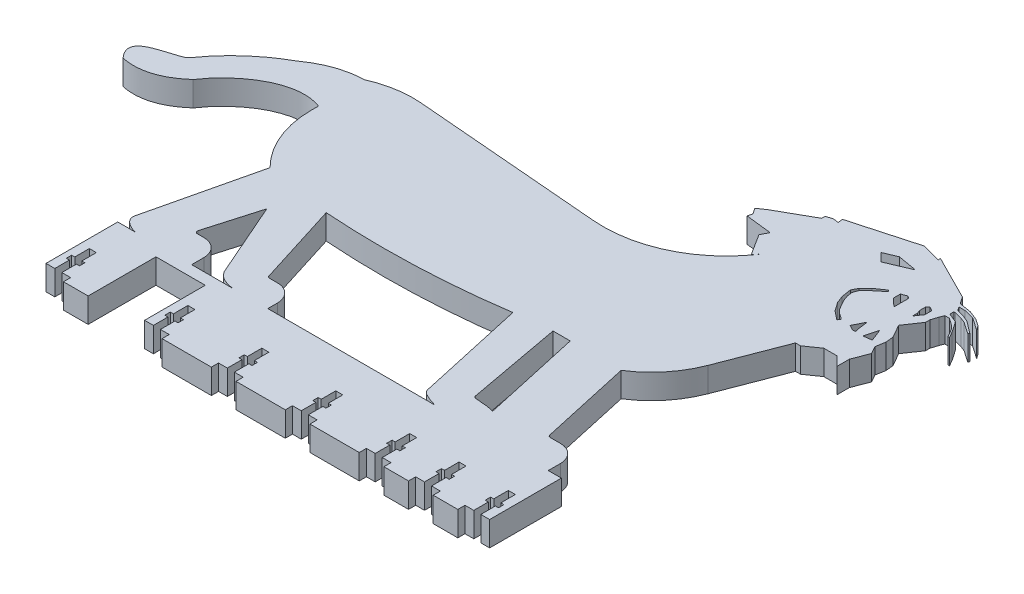
SolidWorks part; units mm, degrees
ref_plane "Front Plane" through (0, 0, 0) normal (0, 0, 1) x (1, 0, 0)
ref_plane "Top Plane" through (0, 0, 0) normal (0, 1, 0) x (1, 0, 0)
ref_plane "Right Plane" through (0, 0, 0) normal (1, 0, 0) x (0, 0, -1)
sketch "Sketch1" plane through (0, 0, 0) normal (0, 1, 0) x (1, 0, 0)
  line L0 (90, -48.4544) -> (80, -48.4544)
  line L1 (90, -48.4544) -> (-90, -48.4544)
  line L2 (90, -48.4544) -> (90, 48.4544)
  line L3 (90, 48.4544) -> (-90, 48.4544)
  line L4 (-90, -48.4544) -> (-90, 48.4544)
  line L5 (90, -48.4544) -> (-90, 48.4544) construction
  line L6 (90, 48.4544) -> (-90, -48.4544) construction
  line L7 (80, -48.4544) -> (80, -51.3617)
  line L8 (80, -51.3617) -> (70, -51.3617)
  line L9 (70, -51.3617) -> (70, -48.4544)
  line L10 (70, -48.4544) -> (60, -48.4544)
  line L11 (60, -48.4544) -> (60, -51.3617)
  line L12 (60, -51.3617) -> (50, -51.3617)
  line L13 (50, -51.3617) -> (50, -48.4544)
  line L14 (50, -48.4544) -> (40, -48.4544)
  line L15 (40, -48.4544) -> (40, -51.3617)
  line L16 (40, -51.3617) -> (20, -51.3617)
  line L17 (20, -51.3617) -> (20, -48.4544)
  line L18 (20, -48.4544) -> (10, -48.4544)
  line L19 (10, -48.4544) -> (10, -51.3617)
  line L20 (10, -51.3617) -> (-10, -51.3617)
  line L21 (-10, -51.3617) -> (-10, -48.4544)
  line L22 (-10, -48.4544) -> (-20, -48.4544)
  line L23 (-20, -48.4544) -> (-20, -51.3617)
  line L24 (-20, -51.3617) -> (-40, -51.3617)
  line L25 (-40, -51.3617) -> (-40, -48.4544)
  line L26 (-40, -48.4544) -> (-50, -48.4544)
  line L27 (-50, -48.4544) -> (-50, -23.8396)
  line L28 (-50, -23.8396) -> (-70, -23.8396)
  line L29 (-70, -23.8396) -> (-70, -48.4544)
  line L30 (-70, -48.4544) -> (-70, -51.3617)
  line L31 (-70, -51.3617) -> (-80, -51.3617)
  line L32 (-80, -51.3617) -> (-80, -48.4544)
  line L33 (-80, -48.4544) -> (-90, -48.4544)
  point P0 (0, 0)
  dimension "D1" = 10
  dimension "D2" = 10
  dimension "D3" = 10
  dimension "D4" = 10
  dimension "D5" = 10
  dimension "D6" = 20
  dimension "D7" = 10
  dimension "D8" = 20
  dimension "D9" = 10
  dimension "D10" = 20
  dimension "D11" = 10
  dimension "D12" = 20
  dimension "D13" = 10
  dimension "D14" = 10
extrude "Boss-Extrude1" add sketch "Sketch1" along normal blind 10 contours L29 L28 L27 L1 L0 L2 L3 L4 | L32 L31 L30 L1 | L25 L24 L23 L1 | L21 L20 L19 L1 | L17 L16 L15 L1 | L13 L12 L11 L1 | L9 L8 L7 L1 region at (1.7425, 0, -1.0498) region at (75, 0, 49.908) region at (55, 0, 49.908) region at (-75, 0, 49.908) region at (30, 0, 49.908) region at (0, 0, 49.908) region at (-30, 0, 49.908)
sketch "Sketch3" plane through (0, 10, 0) normal (0, 1, 0) x (1, 0, 0)
  line L0 (-80, -48.4544) -> (-90, -48.4544) construction
  line L1 (-86.425, -48.4544) -> (-83.575, -48.4544)
  line L2 (-86.425, -48.4544) -> (-86.425, -34.4544)
  line L3 (-86.425, -34.4544) -> (-83.575, -34.4544)
  line L4 (-83.575, -48.4544) -> (-83.575, -34.4544)
  line L5 (-90, -48.4544) -> (-90, 48.4544) construction
  line L6 (-87.675, -40.3544) -> (-82.325, -40.3544)
  line L7 (-87.675, -40.3544) -> (-87.675, -42.5544)
  line L8 (-87.675, -42.5544) -> (-82.325, -42.5544)
  line L9 (-82.325, -40.3544) -> (-82.325, -42.5544)
  line L10 (-46.425, -48.4544) -> (-43.575, -48.4544)
  line L11 (-46.425, -48.4544) -> (-46.425, -34.4544)
  line L12 (-46.425, -34.4544) -> (-43.575, -34.4544)
  line L13 (-43.575, -48.4544) -> (-43.575, -34.4544)
  line L14 (-47.675, -40.3544) -> (-42.325, -40.3544)
  line L15 (-47.675, -40.3544) -> (-47.675, -42.5544)
  line L16 (-47.675, -42.5544) -> (-42.325, -42.5544)
  line L17 (-42.325, -40.3544) -> (-42.325, -42.5544)
  line L18 (-40, -48.4544) -> (-50, -48.4544) construction
  line L19 (-50, -48.4544) -> (-50, -23.8396) construction
  line L20 (-16.425, -48.4544) -> (-13.575, -48.4544)
  line L21 (-16.425, -48.4544) -> (-16.425, -34.4544)
  line L22 (-16.425, -34.4544) -> (-13.575, -34.4544)
  line L23 (-13.575, -48.4544) -> (-13.575, -34.4544)
  line L24 (-17.675, -40.3544) -> (-12.325, -40.3544)
  line L25 (-17.675, -40.3544) -> (-17.675, -42.5544)
  line L26 (-17.675, -42.5544) -> (-12.325, -42.5544)
  line L27 (-12.325, -40.3544) -> (-12.325, -42.5544)
  line L28 (13.575, -48.4544) -> (16.425, -48.4544)
  line L29 (13.575, -48.4544) -> (13.575, -34.4544)
  line L30 (13.575, -34.4544) -> (16.425, -34.4544)
  line L31 (16.425, -48.4544) -> (16.425, -34.4544)
  line L32 (12.325, -40.3544) -> (17.675, -40.3544)
  line L33 (12.325, -40.3544) -> (12.325, -42.5544)
  line L34 (12.325, -42.5544) -> (17.675, -42.5544)
  line L35 (17.675, -40.3544) -> (17.675, -42.5544)
  line L36 (43.575, -48.4544) -> (46.425, -48.4544)
  line L37 (43.575, -48.4544) -> (43.575, -34.4544)
  line L38 (43.575, -34.4544) -> (46.425, -34.4544)
  line L39 (46.425, -48.4544) -> (46.425, -34.4544)
  line L40 (42.325, -40.3544) -> (47.675, -40.3544)
  line L41 (42.325, -40.3544) -> (42.325, -42.5544)
  line L42 (42.325, -42.5544) -> (47.675, -42.5544)
  line L43 (47.675, -40.3544) -> (47.675, -42.5544)
  line L44 (63.575, -48.4544) -> (66.425, -48.4544)
  line L45 (63.575, -48.4544) -> (63.575, -34.4544)
  line L46 (63.575, -34.4544) -> (66.425, -34.4544)
  line L47 (66.425, -48.4544) -> (66.425, -34.4544)
  line L48 (62.325, -40.3544) -> (67.675, -40.3544)
  line L49 (62.325, -40.3544) -> (62.325, -42.5544)
  line L50 (62.325, -42.5544) -> (67.675, -42.5544)
  line L51 (67.675, -40.3544) -> (67.675, -42.5544)
  line L52 (83.575, -48.4544) -> (86.425, -48.4544)
  line L53 (83.575, -48.4544) -> (83.575, -34.4544)
  line L54 (83.575, -34.4544) -> (86.425, -34.4544)
  line L55 (86.425, -48.4544) -> (86.425, -34.4544)
  line L56 (82.325, -40.3544) -> (87.675, -40.3544)
  line L57 (82.325, -40.3544) -> (82.325, -42.5544)
  line L58 (82.325, -42.5544) -> (87.675, -42.5544)
  line L59 (87.675, -40.3544) -> (87.675, -42.5544)
  line L60 (90, -48.4544) -> (80, -48.4544) construction
  line L61 (90, -48.4544) -> (90, 48.4544) construction
  line L62 (70, -48.4544) -> (60, -48.4544) construction
  line L63 (70, -51.3617) -> (70, -48.4544) construction
  line L64 (50, -48.4544) -> (40, -48.4544) construction
  line L65 (50, -51.3617) -> (50, -48.4544) construction
  line L66 (20, -48.4544) -> (10, -48.4544) construction
  line L67 (20, -51.3617) -> (20, -48.4544) construction
  line L68 (-10, -48.4544) -> (-20, -48.4544) construction
  line L69 (-10, -51.3617) -> (-10, -48.4544) construction
  point P20 (-47.675, -41.4544)
  point P33 (-17.675, -41.4544)
  point P42 (12.325, -41.4544)
  point P51 (42.325, -41.4544)
  point P60 (62.325, -41.4544)
  point P69 (82.325, -41.4544)
  dimension "D1" = 2.85
  dimension "D2" = 5.35
  dimension "D3" = 2.2
  dimension "D4" = 14
  dimension "D5" = 2.325
  dimension "D6" = 3.575
  dimension "D7" = 2.85
  dimension "D8" = 5.35
  dimension "D9" = 2.2
  dimension "D10" = 14
  dimension "D11" = 1.25
  dimension "D12" = 5.9
  dimension "D13" = 5.9
  dimension "D14" = 0
  dimension "D15" = 3.575
  dimension "D16" = 2.85
  dimension "D17" = 5.35
  dimension "D18" = 2.2
  dimension "D19" = 14
  dimension "D20" = 1.25
  dimension "D21" = 5.9
  dimension "D22" = 2.85
  dimension "D23" = 5.35
  dimension "D24" = 2.2
  dimension "D25" = 14
  dimension "D26" = 1.25
  dimension "D27" = 5.9
  dimension "D28" = 2.85
  dimension "D29" = 5.35
  dimension "D30" = 2.2
  dimension "D31" = 14
  dimension "D32" = 1.25
  dimension "D33" = 5.9
  dimension "D34" = 2.85
  dimension "D35" = 5.35
  dimension "D36" = 2.2
  dimension "D37" = 14
  dimension "D38" = 1.25
  dimension "D39" = 5.9
  dimension "D40" = 2.85
  dimension "D41" = 5.35
  dimension "D42" = 2.2
  dimension "D43" = 14
  dimension "D44" = 1.25
  dimension "D45" = 5.9
  dimension "D46" = 0
  dimension "D47" = 3.575
  dimension "D48" = 0
  dimension "D49" = 3.575
  dimension "D50" = 0
  dimension "D51" = 3.575
  dimension "D52" = 0
  dimension "D53" = 3.575
  dimension "D54" = 0
  dimension "D55" = 3.575
extrude "Cut-Extrude1" cut sketch "Sketch3" against normal blind 10 contours L4 L3 L2 L1 | L9 L8 L7 L6 | L13 L12 L11 L10 | L17 L16 L15 L14 | L23 L22 L21 L20 | L27 L26 L25 L24 | L29 L30 L31 L28 | L33 L34 L35 L32 | L39 L38 L37 L36 | L42 L43 L40 L41 | L50 L51 L48 L49 | L45 L46 L47 L44 | L55 L54 L53 L52 | L58 L59 L56 L57
sketch "Sketch5" plane through (0, 10, 0) normal (0, 1, 0) x (1, 0, 0)
  line L0 (-90, -19.3517) -> (90, -19.3517)
  line L1 (-90, -48.4544) -> (-90, 48.4544) construction
  line L2 (90, -48.4544) -> (90, 48.4544) construction
  line L3 (90, -19.3517) -> (90, 140.6483)
  line L4 (90, 140.6483) -> (-150, 140.6483)
  line L5 (-150, 140.6483) -> (-150, -19.3517)
  line L6 (-150, -19.3517) -> (-90, -19.3517)
  line L7 (90, 140.6483) -> (125, 140.6483)
  line L8 (125, 140.6483) -> (125, 75.6483)
  line L9 (125, 75.6483) -> (90, 75.6483)
extrude "Boss-Extrude2" add sketch "Sketch5" against normal blind 10 contours L9 L8 L7 L3 | L5 L6 L0 L3 L4 region at (-30, 10, -60.6483) region at (107.5, 10, -108.1483)
sketch "Sketch7" plane through (0, 10, 0) normal (0, 1, 0) x (1, 0, 0)
  line L0 (-90, -19.3517) -> (90, -19.3517)
  line L1 (90, -48.4544) -> (90, 75.6483) construction
  line L2 (90, -19.3517) -> (90, 30.6483)
  line L3 (90, 30.6483) -> (-150, 30.6483)
  line L4 (-150, 140.6483) -> (-150, -19.3517) construction
  line L5 (-150, 30.6483) -> (-150, -19.3517)
  line L6 (-150, -19.3517) -> (-90, -19.3517)
  line L7 (90, 75.6483) -> (72.685, 30.6483)
  line L8 (72.685, 30.6483) -> (-90, 30.6483)
  line L9 (-90, 30.6483) -> (-90, 85.6483)
  line L10 (-90, 85.6483) -> (29.9691, 75.6483)
  line L11 (29.9691, 75.6483) -> (90, 75.6483)
  line L12 (-78.1918, 30.6483) -> (-90, -19.3517)
  line L13 (-90, -19.3517) -> (-60, -19.3517)
  line L14 (-60, -19.3517) -> (-60, -7.3517)
  line L15 (-60, -7.3517) -> (-71, -7.3517)
  line L16 (-71, -7.3517) -> (-60, 30.6483)
  line L17 (-71, 30.6483) -> (-49.1251, -19.3517)
  line L18 (-49.1251, -19.3517) -> (-29.1251, -19.3517)
  line L19 (-29.1251, -19.3517) -> (-29.1251, -8.3517)
  line L20 (-29.1251, -8.3517) -> (-40.1251, -8.3517)
  line L21 (-40.1251, -8.3517) -> (-52.3654, 30.6483)
  line L22 (64.2673, 30.6483) -> (72.685, -7.3517)
  line L23 (72.685, -7.3517) -> (84.685, -7.3517)
  line L24 (84.685, -7.3517) -> (84.685, -19.3517)
  line L25 (84.685, -19.3517) -> (54.685, -19.3517)
  line L26 (54.685, -19.3517) -> (43.609, 30.6483)
  line L27 (43.609, 30.6483) -> (36.609, 30.6483)
  line L28 (36.609, 30.6483) -> (43.8555, -8.6898)
  line L29 (43.8555, -8.6898) -> (52.3232, -8.6898)
  line L30 (52.3232, -8.6898) -> (54.685, -19.3517)
  line L31 (54.685, -19.3517) -> (32.685, -19.3517)
  line L32 (32.685, -19.3517) -> (21.609, 30.6483)
  line L33 (36.609, 75.6483) -> (59.9846, 112.9165)
  line L34 (59.9846, 112.9165) -> (43.609, 120.0898)
  line L35 (43.609, 120.0898) -> (43.609, 140.6483)
  line L36 (-150, 140.6483) -> (125, 140.6483) construction
  line L37 (43.609, 140.6483) -> (125, 140.6483)
  line L38 (125, 140.6483) -> (125, 75.6483)
  line L39 (125, 75.6483) -> (90, 75.6483) construction
  line L40 (125, 140.6483) -> (125, 75.6483) construction
  line L41 (125, 75.6483) -> (90, 75.6483)
  line L42 (-150, 140.6483) -> (43.609, 140.6483)
  line L43 (-150, 140.6483) -> (-150, 30.6483)
  line L44 (90, 30.6483) -> (90, 75.6483)
  line L45 (90, 30.6483) -> (90, -19.3517)
  spline S0 degree 2 poles (-124.7773, 45.9651) (-135.0303, 36.8919) (-146.5024, 39.3052) knots 0 0 0 1 1 1
  spline S1 degree 3 poles (-146.5024, 39.3052) (-155.6059, 49.4717) (-135.7004, 49.6402) (-133.0933, 52.9985) knots 0 0 0 0 1 1 1 1
  spline S2 degree 3 poles (-124.7773, 45.9651) (-117.8679, 56.3801) (-103.2493, 67.0532) (-90, 62.1051) knots 0 0 0 0 1 1 1 1
  spline S3 degree 2 poles (-133.0933, 52.9985) (-124.0498, 65.827) (-110.4095, 73.4115) knots 0 0 0 1 1 1
  spline S4 degree 2 poles (-110.4095, 73.4115) (-100.1544, 80.8869) (-88.5721, 80.6483) knots 0 0 0 1 1 1
extrude "Cut-Extrude2" cut sketch "Sketch7" against normal blind 10 contours L9 L10 L11 L33 L34 L35 L42 L43 L3 | L3 L44 L7 | L23 L24 L0 L2 L3 L22 | L28 L29 L26 L3 | L0 L32 L3 L21 L20 L19 | L3 L5 L6 L12 L8 | L17 L16 L15 L14 L0 region at (-116.9598, 10, -6.3949) region at (-60.678, 10, 4.6118) region at (-60.7011, 10, -101.7209) region at (-8.0236, 10, -6.486) region at (79.6971, 10, -10.9887) region at (44.2254, 10, -10.3572) region at (84.2283, 10, -45.6483)
fillet "Fillet1" radius 40 1 edges at (-90, 5, -85.6483)
fillet "Fillet2" radius 40 1 edges at (-90, 5, -30.6483)
fillet "Fillet3" radius 7 3 edges at (84.685, 5, 7.3517) (-29.1251, 5, 8.3517) (-60, 5, 7.3517)
fillet "Fillet4" radius 40 1 edges at (72.685, 5, -30.6483)
sketch "Sketch8" plane through (0, 10, 0) normal (0, 1, 0) x (1, 0, 0)
  line L0 (-90, -19.3517) -> (-83, -19.3517)
  line L1 (-78.1918, 30.6483) -> (-90, -19.3517) construction
  line L2 (-88.7861, -14.2115) -> (-90, -19.3517)
  line L3 (-49.1251, -19.3517) -> (-43.1251, -19.3517)
  line L4 (-64.3801, 15.5171) -> (-49.1251, -19.3517) construction
  line L5 (-49.1251, -19.3517) -> (-50.9877, -15.0943)
  line L6 (32.685, -19.3517) -> (38.685, -19.3517)
  line L7 (32.685, -19.3517) -> (21.609, 30.6483) construction
  line L8 (32.685, -19.3517) -> (31.3189, -13.1848)
  line L9 (43.609, 30.6483) -> (54.685, -19.3517)
  line L10 (43.8555, -8.6898) -> (52.3232, -8.6898)
  spline S0 degree 2 poles (-83, -19.3517) (-90.7, -17.0676) (-88.1562, -11.5443) knots 0 0 0 1 1 1
  spline S1 degree 2 poles (-43.1251, -19.3517) (-50.1122, -18.6939) (-51.8231, -13.1848) knots 0 0 0 1 1 1
  spline S2 degree 2 poles (38.685, -19.3517) (27.4267, -16.1908) (32.685, -11.5443) knots 0 0 0 1 1 1
  spline S3 degree 2 poles (43.8555, -8.6898) (57.5285, -9.4555) (52.3232, -11.8723) knots 0 0 0 1 1 1
extrude "Cut-Extrude3" cut sketch "Sketch8" against normal blind 10 contours L0 S0 L2 region at (-87.7193, 10, 18.022)
extrude "Cut-Extrude4" cut sketch "Sketch8<4>" against normal blind 10 contours L3 S1 L5 region at (-48.1173, 10, 18.3558)
sketch "Sketch8<4>" plane through (0, 10, 0) normal (0, 1, 0) x (1, 0, 0) same geometry as "Sketch8"
extrude "Cut-Extrude5" cut sketch "Sketch8<5>" against normal blind 10 contours L6 S2 L8 region at (34.3097, 10, 18.4661)
sketch "Sketch8<5>" plane through (0, 10, 0) normal (0, 1, 0) x (1, 0, 0) same geometry as "Sketch8"
extrude "Cut-Extrude6" cut sketch "Sketch8<6>" against normal blind 10 contours L10 S3 L9 region at (49.9539, 10, 8.9972)
sketch "Sketch8<6>" plane through (0, 10, 0) normal (0, 1, 0) x (1, 0, 0) same geometry as "Sketch8"
fillet "Fillet5" radius 50 1 edges at (36.609, 5, -75.6483)
fillet "Fillet6" radius 3 3 edges at (-50.9877, 5, 15.0943) (-88.7861, 5, 14.2115) (32.013, 5, 16.3181)
fillet "Fillet7" radius 1 4 edges at (-71, 5, 7.3517) (-40.1251, 5, 8.3517) (43.8555, 5, 8.6898) (72.685, 5, 7.3517)
sketch "Sketch11" plane through (0, 10, 0) normal (0, 1, 0) x (1, 0, 0)
  line L0 (43.601, 120.2688) -> (43.609, 120.0898)
  line L1 (59.6147, 82.5288) -> (59.6147, 65.7617)
  line L2 (59.6147, 65.7617) -> (77.5081, 78.2745)
  line L3 (77.5081, 78.2745) -> (76.7774, 74.1452)
  line L4 (76.7774, 74.1452) -> (76.7774, 70.2663)
  line L5 (76.7774, 70.2663) -> (91.9017, 80.8427)
  line L6 (91.9017, 80.8427) -> (91.9017, 76.2099)
  line L7 (91.9017, 76.2099) -> (91.9017, 75.5545)
  line L8 (91.9017, 75.5545) -> (97.595, 79.5358)
  line L9 (97.595, 79.5358) -> (102.9869, 79.5358)
  line L10 (102.9869, 79.5358) -> (106.6405, 75.8822)
  line L11 (106.6405, 75.8822) -> (106.6405, 80.8427)
  line L12 (106.6405, 80.8427) -> (109.1476, 87.3816)
  line L13 (109.1476, 87.3816) -> (107.4017, 90.4208)
  line L14 (107.4017, 90.4208) -> (108.0866, 94.2909)
  line L15 (108.0866, 94.2909) -> (107.7441, 97.5005)
  line L16 (107.7441, 97.5005) -> (103.7739, 104.4118)
  line L17 (103.7739, 104.4118) -> (103.7739, 101.3704)
  line L18 (103.7739, 101.3704) -> (108.2747, 107.9773)
  line L19 (108.2747, 107.9773) -> (109.1476, 109.2588)
  line L20 (109.1476, 109.2588) -> (109.1476, 110.9839)
  line L21 (110.04, 113.8455) -> (110.7219, 115.5502)
  line L22 (110.7219, 115.5502) -> (112.4948, 115.5502)
  line L23 (112.4948, 115.5502) -> (114.9836, 113.8455)
  line L24 (114.9836, 113.8455) -> (116.8234, 112.1209)
  line L25 (116.8234, 112.1209) -> (118.6998, 108.7997)
  line L26 (118.6998, 108.7997) -> (119.3134, 108.7997)
  line L27 (119.3134, 108.7997) -> (117.9106, 111.2828)
  line L28 (117.9106, 111.2828) -> (114.9836, 115.5502)
  line L29 (114.9836, 115.5502) -> (111.1804, 117.0715)
  line L30 (111.1804, 117.0715) -> (111.1804, 118.6868)
  line L31 (111.1804, 118.6868) -> (111.8265, 118.6868)
  line L32 (111.8265, 118.6868) -> (114.9836, 117.8792)
  line L33 (114.9836, 117.8792) -> (117.0027, 117.0715)
  line L34 (117.0027, 117.0715) -> (121.7126, 113.8455)
  line L35 (121.7126, 113.8455) -> (121.9452, 114.427)
  line L36 (121.9452, 114.427) -> (117.0027, 118.1501)
  line L37 (117.0027, 118.1501) -> (114.0546, 119.3294)
  line L38 (114.0546, 119.3294) -> (111.5035, 119.982)
  line L39 (111.5035, 119.982) -> (110.5117, 121.4279)
  line L40 (110.5117, 121.4279) -> (113.082, 121.4279)
  line L41 (113.082, 121.4279) -> (115.5287, 120.802)
  line L42 (115.5287, 120.802) -> (117.1572, 120.3853)
  line L43 (117.1572, 120.3853) -> (118.7266, 119.3104)
  line L44 (118.7266, 119.3104) -> (120.7212, 117.9442)
  line L45 (120.7212, 117.9442) -> (122.258, 116.8916)
  line L46 (122.258, 116.8916) -> (121.0675, 118.6273)
  line L47 (121.0675, 118.6273) -> (118.1966, 120.5937)
  line L48 (118.1966, 120.5937) -> (114.5456, 122.0541)
  line L49 (114.5456, 122.0541) -> (110.5117, 122.7224)
  line L50 (110.5117, 122.7224) -> (109.64, 122.8669)
  line L51 (109.64, 122.8669) -> (107.7441, 125.6309)
  line L52 (107.7441, 125.6309) -> (101.8716, 128.5969)
  line L53 (101.8716, 128.5969) -> (93.3621, 132.8946)
  line L54 (93.3621, 132.8946) -> (89.7494, 134.7192)
  line L55 (89.7494, 134.7192) -> (89.7494, 133.8069)
  line L56 (89.7494, 133.8069) -> (81.9898, 135.7921)
  line L57 (81.9898, 135.7921) -> (56.1131, 128.5969)
  line L58 (56.1131, 128.5969) -> (56.343, 126.6031)
  line L59 (56.343, 126.6031) -> (54.2856, 126.944)
  line L60 (54.2856, 126.944) -> (51.5221, 126.1756)
  line L61 (51.5221, 126.1756) -> (51.5221, 124.7439)
  line L62 (51.5221, 124.7439) -> (37.6232, 116.8916)
  line L63 (37.6232, 116.8916) -> (34.4249, 114.6979)
  line L64 (34.4249, 114.6979) -> (36.024, 112.3664)
  line L65 (36.024, 112.3664) -> (35.5364, 110.4603)
  line L66 (35.5364, 110.4603) -> (46.1009, 109.2588)
  line L67 (46.1009, 109.2588) -> (44.5727, 106.2328)
  line L68 (44.5727, 106.2328) -> (59.6147, 82.5288)
  line L69 (58.7524, 65.7617) -> (75.8816, 77.1371)
  line L70 (75.8816, 77.1371) -> (76.7774, 70.2663)
  line L71 (104.6041, 92.2123) -> (102.6559, 97.2028)
  line L72 (43.609, 120.0898) -> (61.9695, 112.3664)
  line L73 (61.9695, 112.3664) -> (50.006, 97.6707)
  line L74 (102.6559, 97.2028) -> (101.268, 91.7774)
  line L75 (101.268, 91.7774) -> (104.6041, 92.2123)
  line L76 (98.2333, 91.9421) -> (97.773, 93.6415)
  line L77 (97.773, 93.6415) -> (97.2699, 97.5005)
  line L78 (97.2699, 97.5005) -> (94.9253, 92.8583)
  line L79 (94.9253, 92.8583) -> (97.2699, 91.6742)
  line L80 (97.2699, 91.6742) -> (98.2333, 91.9421)
  line L81 (94.1044, 114.1185) -> (94.1044, 111.2568)
  line L82 (94.1044, 111.2568) -> (97.3117, 108.2503)
  line L83 (97.3117, 108.2503) -> (97.3117, 114.1185)
  line L84 (97.3117, 114.1185) -> (96.4025, 114.9708)
  line L85 (96.4025, 114.9708) -> (94.1044, 114.1185)
  line L86 (103.7739, 114.6769) -> (103.7739, 112.2447)
  line L87 (103.7739, 112.2447) -> (104.2827, 110.8726)
  line L88 (104.2827, 110.8726) -> (104.2827, 108.8087)
  line L89 (104.2827, 108.8087) -> (106.3309, 111.8152)
  line L90 (106.3309, 111.8152) -> (106.3309, 114.6769)
  line L91 (106.3309, 114.6769) -> (104.6433, 115.5292)
  line L92 (104.6433, 115.5292) -> (103.7739, 114.6769)
  line L93 (88.673, 125.6309) -> (78.8206, 121.4279)
  line L94 (78.8206, 121.4279) -> (75.5562, 124.7577)
  line L95 (75.5562, 124.7577) -> (80.7717, 126.9827)
  line L96 (80.7717, 126.9827) -> (88.673, 125.6309)
  line L97 (110.04, 113.8455) -> (109.1476, 110.9839)
  line L98 (91.9017, 75.5545) -> (125, 75.6483)
  line L99 (125, 75.6483) -> (125, 80.8427)
  line L100 (125, 140.6483) -> (125, 75.6483) construction
  line L101 (125, 80.8427) -> (125, 140.6483)
  line L102 (125, 140.6483) -> (43.609, 140.6483)
  line L103 (43.609, 140.6483) -> (43.601, 120.2688)
extrude "Cut-Extrude7" cut sketch "Sketch11" against normal blind 10 contours L102 L103 L62 L61 L60 L59 L58 L57 L56 L55 L54 L53 L52 L51 L50 L49 L48 L47 L46 L45 L44 L43 L42 L41 L40 L39 L38 L37 L36 L35 L34 L33 L32 L31 L30 L29 L28 L27 L26 L25 L24 L23 L22 L21 L97 L20 L19 L18 L16 L15 L14 | L84 L85 L81 L82 L83 | L91 L92 L86 L87 L88 L89 L90 | L96 L93 L94 L95 | L74 L75 L71 | L77 L78 L79 L80 L76 region at (44.6473, 10, -130.4582) region at (95.8964, 10, -112.0768) region at (105.0076, 10, -112.7411)
extrude "Boss-Extrude3" add sketch "Sketch11<4>" against normal blind 10 contours L73 L72 L0 L62 L63 L64 L65 L66 L67 L68 region at (48.3801, 10, -110.8005)
sketch "Sketch11<4>" plane through (0, 10, 0) normal (0, 1, 0) x (1, 0, 0) same geometry as "Sketch11"
sketch "Sketch12" plane through (0, 10, 0) normal (0, 1, 0) x (1, 0, 0)
  line L1 (-40.345, -7.6511) -> (-52.3654, 30.6483) construction
  line L2 (31.7757, -15.2468) -> (21.609, 30.6483) construction
  line L3 (21.9758, 28.9928) -> (21.4199, 43.5949)
  line L4 (21.4199, 43.5949) -> (-57.4773, 40.5917)
  line L5 (-57.4773, 40.5917) -> (-50.9742, 26.2159)
  spline S0 degree 2 poles (-50.9742, 26.2159) (-0.2358, 22.6879) (48.8065, 34.099) knots 0 0 0 1 1 1
extrude "Boss-Extrude4" add sketch "Sketch12" against normal blind 10 contours L3 L4 L5 region at (-16.1367, 10, -34.2926)
sketch "Sketch13" plane through (0, 10, 0) normal (0, 1, 0) x (1, 0, 0)
  line L0 (90.2963, 113.0887) -> (90.8465, 112.5385)
  line L1 (90.8465, 112.5385) -> (87.6105, 109.8527)
  line L2 (87.6105, 109.8527) -> (85.3395, 107.9677)
  line L3 (85.3395, 107.9677) -> (84.3048, 106.547)
  line L4 (84.3048, 106.547) -> (83.7373, 104.7194)
  line L5 (83.7373, 104.7194) -> (84.021, 102.7472)
  line L6 (84.021, 102.7472) -> (84.8221, 100.4864)
  line L7 (90.2507, 93.7991) -> (91.0585, 93.1539)
  line L8 (91.0585, 93.1539) -> (90.2507, 92.1426)
  line L9 (90.2507, 92.1426) -> (86.739, 94.9474)
  line L10 (86.739, 94.9474) -> (84.3048, 98.447)
  line L11 (84.3048, 98.447) -> (83.1594, 101.4296)
  line L12 (83.1594, 101.4296) -> (82.5064, 105.3899)
  line L13 (82.5064, 105.3899) -> (83.7373, 107.7299)
  line L14 (83.7373, 107.7299) -> (86.3534, 110.346)
  line L15 (86.3534, 110.346) -> (90.2963, 113.0887)
  line L16 (84.8221, 100.4864) -> (85.9615, 98.447)
  line L17 (85.9615, 98.447) -> (87.0357, 96.5242)
  line L18 (87.0357, 96.5242) -> (88.559, 94.9474)
  line L19 (88.559, 94.9474) -> (90.2507, 93.7991)
  line L20 (90.2507, 93.7991) -> (90.1463, 93.8004)
extrude "Cut-Extrude8" cut sketch "Sketch13" against normal blind 10 contours L19 L18 L17 L16 L6 L5 L4 L3 L2 L1 L0 L15 L14 L13 L12 L11 L10 L9 L8 L7 region at (90.4114, 10, -112.6536)
